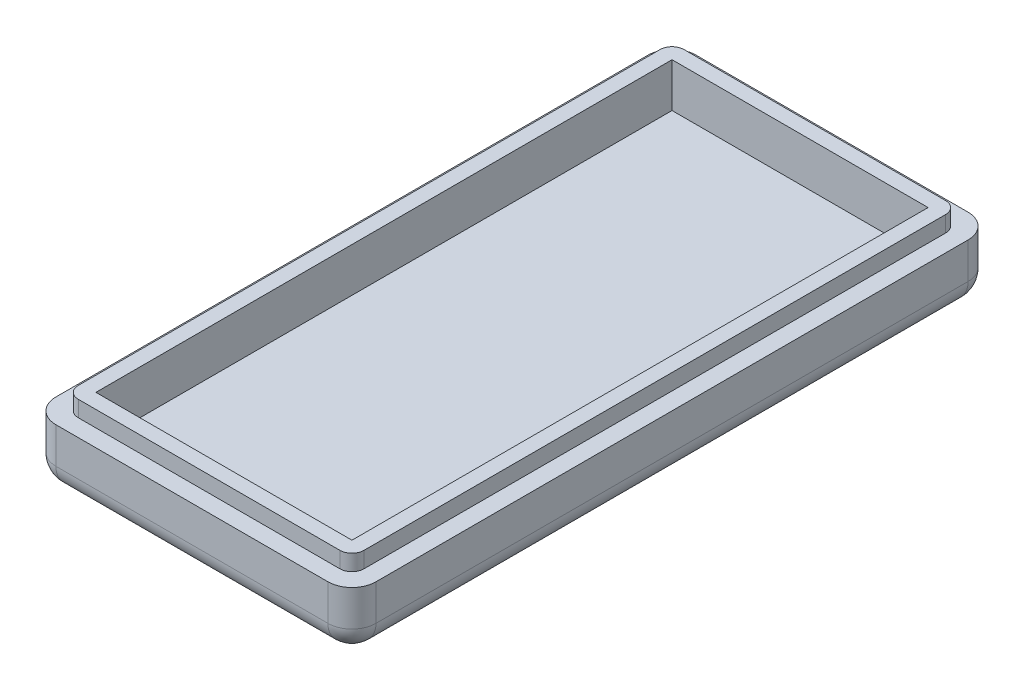
SolidWorks part; units mm, degrees
material "ABS"
ref_plane "Front Plane" through (0, 0, 0) normal (0, 0, 1) x (1, 0, 0)
ref_plane "Top Plane" through (0, 0, 0) normal (0, 1, 0) x (1, 0, 0)
ref_plane "Right Plane" through (0, 0, 0) normal (1, 0, 0) x (0, 0, -1)
sketch "Sketch1" plane through (0, 0, 0) normal (0, 0, 1) x (1, 0, 0)
  line L1 (0, 0) -> (40, 0)
  line L2 (0, 0) -> (0, 7.5)
  line L3 (0, 7.5) -> (40, 7.5)
  line L4 (40, 0) -> (40, 7.5)
  dimension "D1" = 40
  dimension "D2" = 7.5
extrude "Boss-Extrude1" add sketch "Sketch1" along normal blind 80
shell "Shell1" thickness 4 removed face at (20, 7.5, 40)
fillet "Fillet1" radius 3 8 edges at (20, 0, 80) (0, 3.75, 80) (0, 0, 40) (40, 3.75, 80) (40, 0, 40) (40, 3.75, 0) (20, 0, 0) (0, 3.75, 0)
sketch "Sketch2" plane through (0, 7.5, 0) normal (0, 1, 0) x (1, 0, 0)
  line L10 (36, -4) -> (4, -4)
  line L11 (4, -4) -> (4, -76)
  line L12 (4, -76) -> (36, -76)
  line L13 (36, -76) -> (36, -4)
  line L14 (2.15, -77.85) -> (37.85, -77.85)
  line L15 (37.85, -77.85) -> (37.85, -2.15)
  line L16 (37.85, -2.15) -> (2.15, -2.15)
  line L17 (2.15, -2.15) -> (2.15, -77.85)
  line L18 (3.65, -77.85) -> (36.35, -77.85)
  line L19 (37.85, -76.35) -> (37.85, -3.65)
  line L20 (36.35, -2.15) -> (3.65, -2.15)
  line L21 (2.15, -3.65) -> (2.15, -76.35)
  line L22 (2.15, -2.15) -> (2.15, -77.85) construction
  line L23 (2.15, -77.85) -> (37.85, -77.85) construction
  line L24 (37.85, -77.85) -> (37.85, -2.15) construction
  line L25 (37.85, -2.15) -> (2.15, -2.15) construction
  arc A0 (2.15, -76.35) -> (3.65, -77.85) centre (3.65, -76.35) ccw
  arc A1 (37.85, -76.35) -> (36.35, -77.85) centre (36.35, -76.35) cw
  arc A2 (36.35, -2.15) -> (37.85, -3.65) centre (36.35, -3.65) cw
  arc A3 (2.15, -3.65) -> (3.65, -2.15) centre (3.65, -3.65) cw
  dimension "D3" = 1.5
  dimension "D1" = 1.85
  dimension "D2" = 1.85
extrude "Boss-Extrude2" add sketch "Sketch2" along normal blind 2
